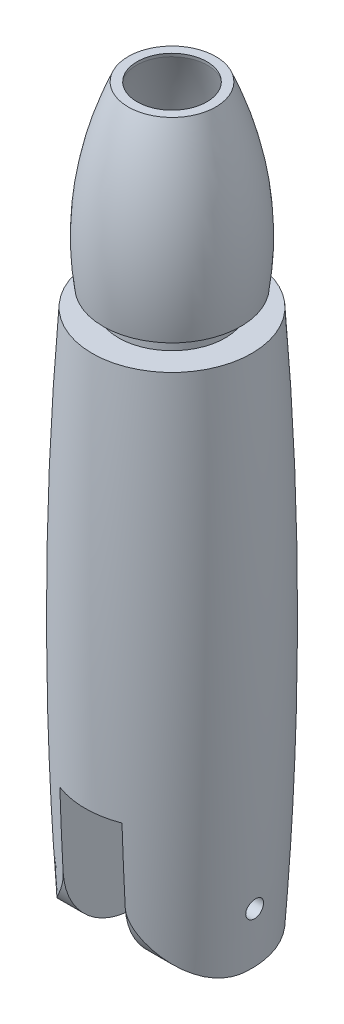
SolidWorks part; units mm, degrees
ref_plane "Front Plane" through (0, 0, 0) normal (0, 0, 1) x (1, 0, 0)
ref_plane "Top Plane" through (0, 0, 0) normal (0, 1, 0) x (1, 0, 0)
ref_plane "Right Plane" through (0, 0, 0) normal (1, 0, 0) x (0, 0, -1)
sketch "Sketch1" plane through (0, 0, 0) normal (0, 0, 1) x (1, 0, 0)
  line L0 (0, 60) -> (3, 60)
  line L3 (9, 26) -> (9, 14)
  line L6 (3, 0) -> (0, 0)
  line L7 (3, 60) -> (9, 60) construction
  line L8 (9, 60) -> (9, 26)
  line L9 (3, 0) -> (9, 0)
  line L10 (9, 0) -> (9, 14)
  line L11 (3, 60) -> (3, 62)
  line L12 (9, 60) -> (9, 82)
  line L13 (3, 62) -> (1.25, 62)
  line L14 (4.07, 82) -> (5.07, 82)
  line L15 (5.07, 82) -> (4.9901, 81.6084)
  line L16 (2.2371, 71.8457) -> (9, 71.8457)
  arc A0 (0, 60) -> (0, 0) centre (449.5, 30) ccw
  spline S0 degree 2 poles (4.07, 82) (-0.1501, 72.0854) (1.25, 62) knots 0 0 0 1 1 1
  spline S1 degree 1 poles (4.9901, 81.6084) (2.2405, 62.1375) knots 0 0 1 1 construction
  spline S2 degree 3 poles (4.9901, 81.6084) (4.6506, 80.8106) (4.0148, 79.1807) (3.1108, 76.3391) (2.4584, 73.4861) (2.0069, 70.2438) (1.8165, 66.613) (2.0156, 63.7572) (2.2405, 62.1375) knots 0 0 0 0 0.125 0.25 0.440447 0.565447 0.75 1 1 1 1 only from (4.9901, 81.6084) to (2.2371, 71.8457)
  point P1 (-1, 30)
  dimension "D1" = 60
  dimension "D2" = 9
  dimension "D3" = 10
  dimension "D4" = 2
  dimension "D5" = 7.75
  dimension "D6" = 4.93
  dimension "D7" = 22
  dimension "D8" = 6
  dimension "D9" = 1
  dimension "D10" = 1
revolve "Revolve1" add sketch "Sketch1" angle 360 about L3 region at (4.2729, 35.5372, 0)
sketch "Sketch2" plane through (0, 0, 0) normal (0, 0, 1) x (1, 0, 0)
  line L7 (5.5, 0) -> (5.5, 16)
  line L14 (5.5, 0) -> (12.5, 0)
  line L17 (0, 0) -> (18, 0)
  line L31 (0, 0) -> (18, 0) construction
  line L32 (5.5, 16) -> (12.5, 16)
  line L33 (12.5, 16) -> (12.5, 0)
  point P9 (9, 0)
  point P11 (9, 0)
  dimension "D4" = 16
  dimension "D5" = 7
extrude "Cut-Extrude1" cut sketch "Sketch2" against normal blind 7.5 and the other way through all contours L33 L32 L7 region at (9, 8, 0)
sketch "Sketch3" plane through (0, 0, 0) normal (1, 0, 0) x (0, 0, -1)
  line L0 (9, 60) -> (-9, 60) construction
  line L5 (-8.2916, 0) -> (9, 0) construction
  line L7 (-8.2916, 0) -> (9, 0)
  circle A0 centre (0, 54) radius 1
  circle A1 centre (0, 6) radius 1
  arc A6 (-8.7686, 7.5712) -> (-0.7801, 0) centre (-0.7801, 8) ccw
  spline S0 degree 3 poles (832.7196, -541.0177) (163.2955, -385.0431) (3.9095, -195.3903) (-8.6003, 4.6244) (-8.6599, 5.6158) (-8.7159, 6.6074) (-8.7524, 7.2685) (-8.7707, 7.6071) (-25.2839, 320.5647) (315.1329, 645.0631) (324.8962, 958.5589) knots -37.460193 -37.460193 -37.460193 -37.460193 0.25 0.25 0.375 0.4375 0.4375 0.5 0.5 58.718393 58.718393 58.718393 58.718393 only from (-8.2916, 0) to (-9.1349, 16) construction
  spline S1 degree 3 poles (-8.2916, 0) (-8.3872, 1.3208) (-8.4764, 2.6419) (-8.6003, 4.6244) (-8.6599, 5.6158) (-8.7159, 6.6074) (-8.7524, 7.2685) (-8.7707, 7.6071) (-8.9301, 10.6276) (-9.0454, 13.3134) (-9.1349, 16) knots 0 0 0 0 0.25 0.25 0.375 0.4375 0.4375 0.5 0.5 1 1 1 1
  dimension "D1" = 2
  dimension "D2" = 6
  dimension "D3" = 8
  dimension "D4" = 6
extrude "Cut-Extrude2" cut sketch "Sketch3" against normal through all both and the other way through all contours A1 | A6 L7 region at (0, 1.675, 6.7468) region at (0, 6, 0)
sketch "Sketch5" plane through (0, 71.8457, 0) normal (0, 1, 0) x (1, 0, 0)
  line L0 (5.5, 4) -> (12.5, 4) construction
  line L3 (12.5, -9.1349) -> (12.5, 7.5) construction
  line L4 (5.5, -9.1349) -> (5.5, 7.5) construction
  circle A0 centre (9, 4) radius 0.5
  circle A1 centre (9, -3) radius 0.5
  point P12 (9, 4)
  dimension "D1" = 1
  dimension "D2" = 1
  dimension "D3" = 4
  dimension "D4" = 3
extrude "Cut-Extrude4" cut sketch "Sketch5" against normal up to next
sketch "Sketch6" plane through (0, 0, -7.5) normal (0, 0, 1) x (1, 0, 0)
  line L1 (5.5, 0) -> (12.5, 0)
  line L2 (5.5, 0) -> (5.5, 6)
  line L3 (5.5, 6) -> (12.5, 6)
  line L4 (12.5, 0) -> (12.5, 6)
  dimension "D1" = 6
extrude "Cut-Extrude5" cut sketch "Sketch6" against normal through all
